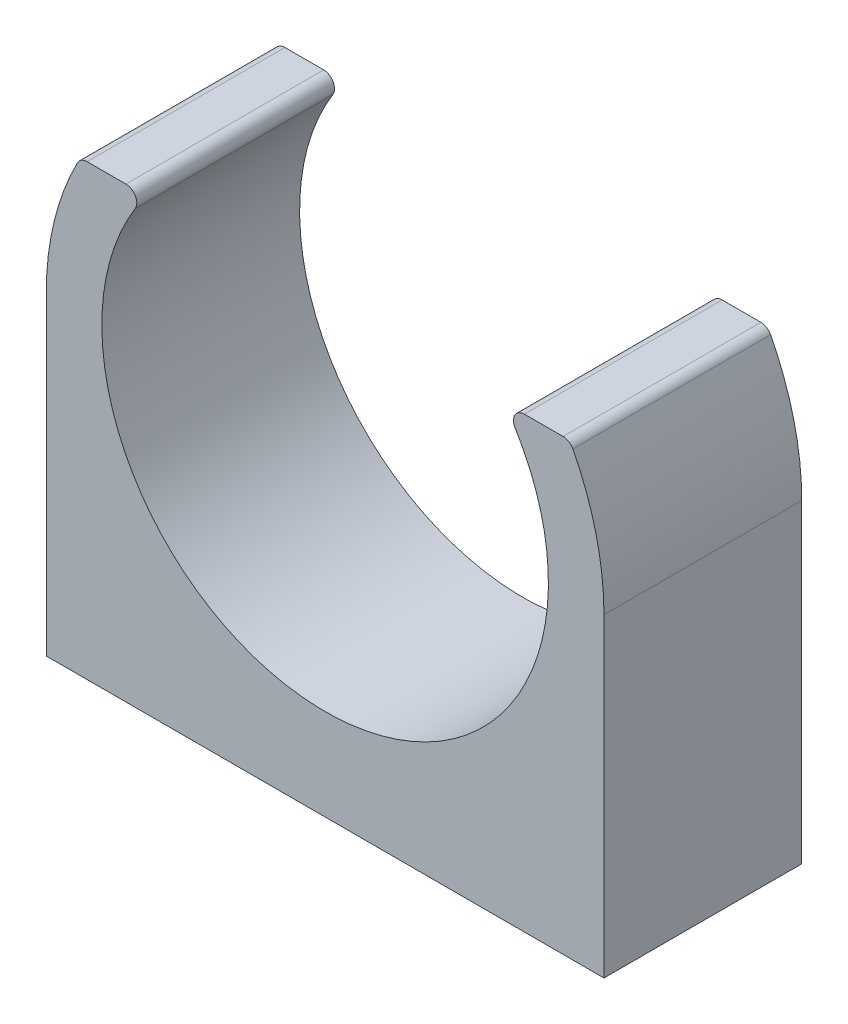
SolidWorks part; units mm, degrees
ref_plane "Front Plane" through (0, 0, 0) normal (0, 0, 1) x (1, 0, 0)
ref_plane "Top Plane" through (0, 0, 0) normal (0, 1, 0) x (1, 0, 0)
ref_plane "Right Plane" through (0, 0, 0) normal (1, 0, 0) x (0, 0, -1)
sketch "Sketch1" plane through (0, 0, 0) normal (0, 0, 1) x (1, 0, 0)
  line L0 (-21.15, 0) -> (21.15, 0)
  line L1 (-21.15, 0) -> (-21.15, 20.1112)
  line L3 (21.15, 0) -> (21.15, 20.1112)
  line L6 (-18.5498, 30.2712) -> (-13.5502, 30.2712)
  line L7 (13.5502, 30.2712) -> (18.5498, 30.2712)
  line L11 (-21.15, 20.1112) -> (21.15, 20.1112) construction
  line L12 (-21.15, 0) -> (21.15, 0)
  line L13 (-21.15, 0) -> (-21.15, -3.75)
  line L14 (21.15, 0) -> (21.15, -3.75)
  line L15 (-21.15, -3.75) -> (21.15, -3.75)
  arc A0 (-13.5502, 30.2712) -> (13.5502, 30.2712) centre (0, 20.1112) ccw
  arc A1 (-18.5498, 30.2712) -> (-21.15, 20.1112) centre (0, 20.1112) ccw
  arc A2 (-16.9216, 32.7991) -> (16.9216, 32.7991) centre (0, 20.1112) ccw construction
  arc A3 (21.15, 20.1112) -> (18.5498, 30.2712) centre (0, 20.1112) ccw
  point P2 (0, 20.1112)
  dimension "D6" = 33.8724
  dimension "D1" = 3.175
  dimension "D2" = 42.3
  dimension "D3" = 10.16
  dimension "D4" = 3.75
extrude "Boss-Extrude1" add sketch "Sketch1" along normal blind 15 contours L3 A3 L7 A0 L6 A1 L1 L0 | L13 L15 L14 L0 region at (-20.6298, 10.0556, 0) region at (0, -1.875, 0)
fillet "Fillet1" radius 0.8255 4 edges at (13.5502, 30.2712, 7.5) (-13.5502, 30.2712, 7.5) (18.5498, 30.2712, 7.5) (-18.5498, 30.2712, 7.5)
